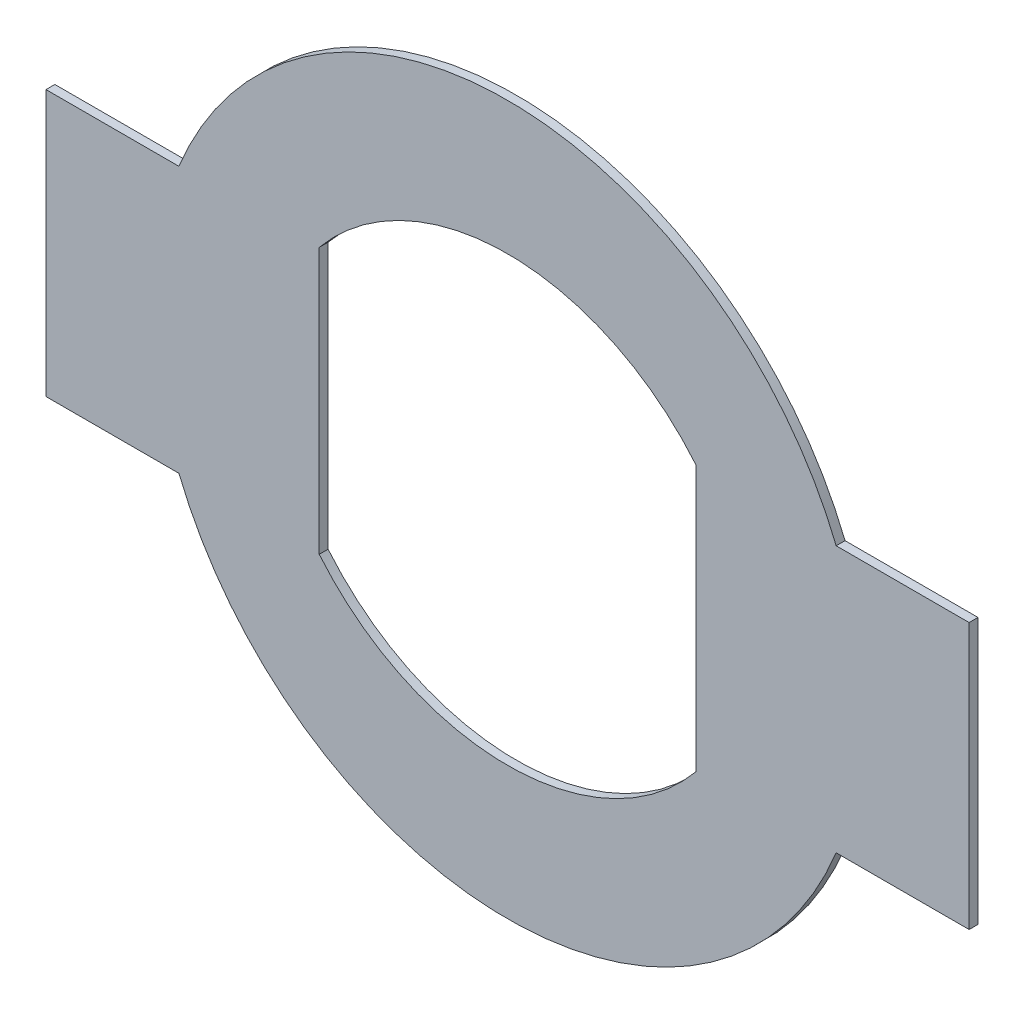
SolidWorks part; units mm, degrees
ref_plane "Front Plane" through (0, 0, 0) normal (0, 0, 1) x (1, 0, 0)
ref_plane "Top Plane" through (0, 0, 0) normal (0, 1, 0) x (1, 0, 0)
ref_plane "Right Plane" through (0, 0, 0) normal (1, 0, 0) x (0, 0, -1)
sketch "Sketch1" plane through (0, 0, 0) normal (0, 0, 1) x (1, 0, 0)
  line L0 (0, 0) -> (11.0762, 0) construction
  line L1 (7.4162, 3) -> (10.4162, 3)
  line L2 (10.4162, 3) -> (10.4162, -3)
  line L3 (10.4162, -3) -> (7.4162, -3)
  line L5 (-10.4162, -3) -> (-7.4162, -3)
  line L6 (-10.4162, 3) -> (-10.4162, -3)
  line L7 (-7.4162, 3) -> (-10.4162, 3)
  line L8 (4.25, 0) -> (-4.25, 0) construction
  line L9 (-4.25, 3) -> (-4.25, -3)
  line L10 (4.25, 3) -> (4.25, -3)
  arc A0 (7.4162, 3) -> (-7.4162, 3) centre (0, 0) ccw
  arc A1 (-7.4162, -3) -> (7.4162, -3) centre (0, 0) ccw
  arc A2 (-4.25, 3) -> (4.25, 3) centre (0, -0.5156) cw
  arc A3 (-4.25, -3) -> (4.25, -3) centre (0, 0.5156) ccw
  dimension "D1" = 16
  dimension "D4" = 1.0313
  dimension "D6" = 5.5156
  dimension "D2" = 6
  dimension "D3" = 3
  dimension "D5" = 8.5
sheet metal parameters "Sheet-Metal1" thickness 0.2 parameters "D1"=1
base flange "Base-Flange1" sketch "Sketch1" thickness 0.2 reverse thickness direction no parameters "D1"=1
flat pattern "Flat-Pattern1" [suppressed]
sketch "Bend-Lines1" plane through (0, 0, 0) normal (0, 1, 0) x (-1, 0, 0)
sketch3d "Bounding-Box1" [suppressed]
  line L0 (10.4162, -8, 0) -> (-10.4162, -8, 0) construction
  line L1 (10.4162, 8, 0) -> (-10.4162, 8, 0) construction
  line L2 (10.4162, -8, 0) -> (10.4162, 8, 0) construction
  line L3 (-10.4162, -8, 0) -> (-10.4162, 8, 0) construction
